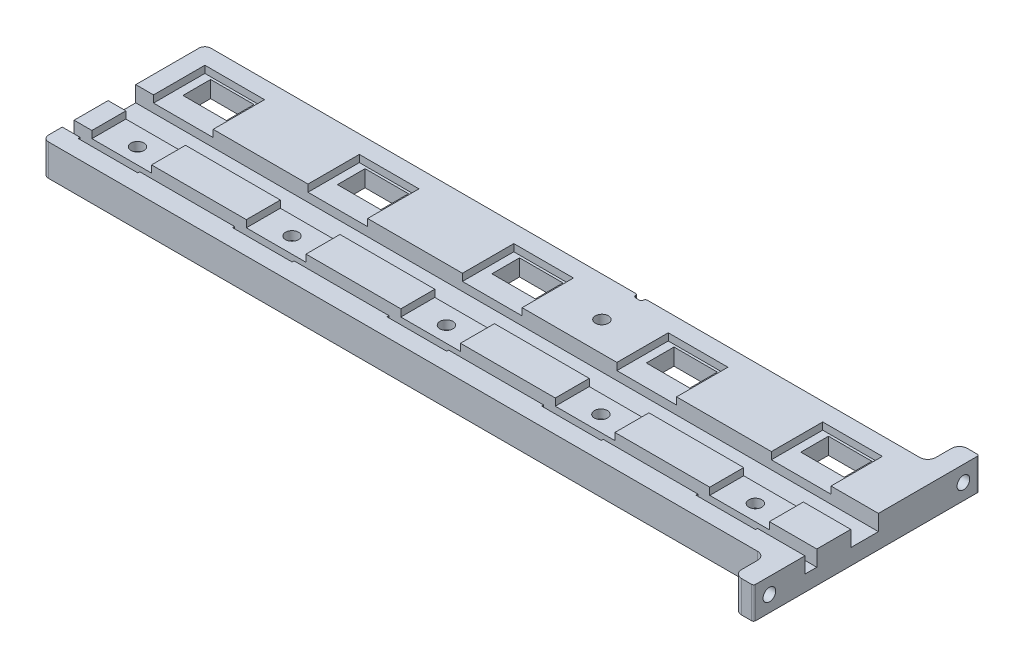
SolidWorks part; units mm, degrees
ref_plane "Front Plane" through (0, 0, 0) normal (0, 0, 1) x (1, 0, 0)
ref_plane "Top Plane" through (0, 0, 0) normal (0, 1, 0) x (1, 0, 0)
ref_plane "Right Plane" through (0, 0, 0) normal (1, 0, 0) x (0, 0, -1)
sketch "Sketch1" plane through (0, 0, 0) normal (0, 1, 0) x (1, 0, 0)
  line L0 (0, 20.55) -> (0, -20.55) construction
  line L1 (-188, 20.55) -> (188, 20.55)
  line L2 (-188, 20.55) -> (-188, -20.55)
  line L3 (-188, -20.55) -> (188, -20.55)
  line L4 (188, 20.55) -> (188, -20.55)
  line L5 (-188, 20.55) -> (188, -20.55) construction
  line L6 (-188, -20.55) -> (188, 20.55) construction
  line L7 (19.55, 20.55) -> (19.55, -20.55) construction
  line L8 (39.3017, 24.4025) -> (39.3017, -16.4975) construction
  line L9 (14.05, 15.45) -> (25.05, 15.45)
  line L10 (14.05, 15.45) -> (14.05, 8.45)
  line L11 (14.05, 8.45) -> (25.05, 8.45)
  line L12 (25.05, 15.45) -> (25.05, 8.45)
  line L13 (14.05, 15.45) -> (25.05, 8.45) construction
  line L14 (14.05, 8.45) -> (25.05, 15.45) construction
  line L15 (12.5, 15.55) -> (26.6, 15.55)
  line L16 (12.5, 15.55) -> (12.5, -15.55)
  line L17 (12.5, -15.55) -> (26.6, -15.55)
  line L18 (26.6, 15.55) -> (26.6, -15.55)
  line L19 (12.5, 15.55) -> (26.6, -15.55) construction
  line L20 (12.5, -15.55) -> (26.6, 15.55) construction
  line L21 (58.65, 20.45) -> (58.65, -20.45) construction
  line L22 (53.15, 15.45) -> (64.15, 15.45)
  line L23 (53.15, 15.45) -> (53.15, 8.45)
  line L24 (53.15, 8.45) -> (64.15, 8.45)
  line L25 (64.15, 15.45) -> (64.15, 8.45)
  line L26 (53.15, 15.45) -> (64.15, 8.45) construction
  line L27 (53.15, 8.45) -> (64.15, 15.45) construction
  line L28 (51.6, 15.55) -> (65.7, 15.55)
  line L29 (51.6, 15.55) -> (51.6, -15.55)
  line L30 (51.6, -15.55) -> (65.7, -15.55)
  line L31 (65.7, 15.55) -> (65.7, -15.55)
  line L32 (51.6, 15.55) -> (65.7, -15.55) construction
  line L33 (51.6, -15.55) -> (65.7, 15.55) construction
  line L34 (2.5, 20.55) -> (2.5, -20.35) construction
  line L35 (-19.55, 20.45) -> (-19.55, -20.45) construction
  line L36 (-25.05, 15.45) -> (-14.05, 15.45)
  line L37 (-25.05, 15.45) -> (-25.05, 8.45)
  line L38 (-25.05, 8.45) -> (-14.05, 8.45)
  line L39 (-14.05, 15.45) -> (-14.05, 8.45)
  line L40 (-25.05, 15.45) -> (-14.05, 8.45) construction
  line L41 (-25.05, 8.45) -> (-14.05, 15.45) construction
  line L42 (-26.6, 15.55) -> (-12.5, 15.55)
  line L43 (-26.6, 15.55) -> (-26.6, -15.55)
  line L44 (-26.6, -15.55) -> (-12.5, -15.55)
  line L45 (-12.5, 15.55) -> (-12.5, -15.55)
  line L46 (-26.6, 15.55) -> (-12.5, -15.55) construction
  line L47 (-26.6, -15.55) -> (-12.5, 15.55) construction
  line L48 (78.3899, 8.6881) -> (78.3899, -32.2119) construction
  line L49 (97.75, 36.3335) -> (97.75, -36.3335) construction
  line L50 (92.25, 15.45) -> (103.25, 15.45)
  line L51 (92.25, 15.45) -> (92.25, 8.45)
  line L52 (92.25, 8.45) -> (103.25, 8.45)
  line L53 (103.25, 15.45) -> (103.25, 8.45)
  line L54 (92.25, 15.45) -> (103.25, 8.45) construction
  line L55 (92.25, 8.45) -> (103.25, 15.45) construction
  line L56 (90.7, 15.55) -> (104.8, 15.55)
  line L57 (90.7, 15.55) -> (90.7, -15.55)
  line L58 (90.7, -15.55) -> (104.8, -15.55)
  line L59 (104.8, 15.55) -> (104.8, -15.55)
  line L60 (90.7, 15.55) -> (104.8, -15.55) construction
  line L61 (90.7, -15.55) -> (104.8, 15.55) construction
  line L62 (-4.3132, 22.4762) -> (-4.3132, -18.4238) construction
  line L63 (-58.65, 23.8204) -> (-58.65, -23.8204) construction
  line L64 (-64.15, 15.45) -> (-53.15, 15.45)
  line L65 (-64.15, 15.45) -> (-64.15, 8.45)
  line L66 (-64.15, 8.45) -> (-53.15, 8.45)
  line L67 (-53.15, 15.45) -> (-53.15, 8.45)
  line L68 (-64.15, 15.45) -> (-53.15, 8.45) construction
  line L69 (-64.15, 8.45) -> (-53.15, 15.45) construction
  line L70 (-65.7, 15.55) -> (-51.6, 15.55)
  line L71 (-65.7, 15.55) -> (-65.7, -15.55)
  line L72 (-65.7, -15.55) -> (-51.6, -15.55)
  line L73 (-51.6, 15.55) -> (-51.6, -15.55)
  line L74 (-65.7, 15.55) -> (-51.6, -15.55) construction
  line L75 (-65.7, -15.55) -> (-51.6, 15.55) construction
  line L76 (-4.3132, 22.4762) -> (-4.3132, -18.4238) construction
  line L77 (-97.75, 23.4723) -> (-97.75, -23.4723) construction
  line L78 (-103.25, 15.45) -> (-92.25, 15.45)
  line L79 (-103.25, 15.45) -> (-103.25, 8.45)
  line L80 (-103.25, 8.45) -> (-92.25, 8.45)
  line L81 (-92.25, 15.45) -> (-92.25, 8.45)
  line L82 (-103.25, 15.45) -> (-92.25, 8.45) construction
  line L83 (-103.25, 8.45) -> (-92.25, 15.45) construction
  line L84 (-104.8, 15.55) -> (-90.7, 15.55)
  line L85 (-104.8, 15.55) -> (-104.8, -15.55)
  line L86 (-104.8, -15.55) -> (-90.7, -15.55)
  line L87 (-90.7, 15.55) -> (-90.7, -15.55)
  line L88 (-104.8, 15.55) -> (-90.7, -15.55) construction
  line L89 (-104.8, -15.55) -> (-90.7, 15.55) construction
  line L90 (-4.3132, 22.4762) -> (-4.3132, -18.4238) construction
  line L91 (-136.85, 23.6913) -> (-136.85, -23.6913) construction
  line L92 (-142.35, 15.45) -> (-131.35, 15.45)
  line L93 (-142.35, 15.45) -> (-142.35, 8.45)
  line L94 (-142.35, 8.45) -> (-131.35, 8.45)
  line L95 (-131.35, 15.45) -> (-131.35, 8.45)
  line L96 (-142.35, 15.45) -> (-131.35, 8.45) construction
  line L97 (-142.35, 8.45) -> (-131.35, 15.45) construction
  line L98 (-143.9, 15.55) -> (-129.8, 15.55)
  line L99 (-143.9, 15.55) -> (-143.9, -15.55)
  line L100 (-143.9, -15.55) -> (-129.8, -15.55)
  line L101 (-129.8, 15.55) -> (-129.8, -15.55)
  line L102 (-143.9, 15.55) -> (-129.8, -15.55) construction
  line L103 (-143.9, -15.55) -> (-129.8, 15.55) construction
  line L104 (-4.3132, 22.4762) -> (-4.3132, -18.4238) construction
  line L105 (-175.95, 23.8593) -> (-175.95, -23.8593) construction
  line L106 (-181.45, 15.45) -> (-170.45, 15.45)
  line L107 (-181.45, 15.45) -> (-181.45, 8.45)
  line L108 (-181.45, 8.45) -> (-170.45, 8.45)
  line L109 (-170.45, 15.45) -> (-170.45, 8.45)
  line L110 (-181.45, 15.45) -> (-170.45, 8.45) construction
  line L111 (-181.45, 8.45) -> (-170.45, 15.45) construction
  line L112 (-183, 15.55) -> (-168.9, 15.55)
  line L113 (-183, 15.55) -> (-183, -15.55)
  line L114 (-183, -15.55) -> (-168.9, -15.55)
  line L115 (-168.9, 15.55) -> (-168.9, -15.55)
  line L116 (-183, 15.55) -> (-168.9, -15.55) construction
  line L117 (-183, -15.55) -> (-168.9, 15.55) construction
  line L118 (-4.3132, 22.4762) -> (-4.3132, -18.4238) construction
  line L119 (136.85, 22.8512) -> (136.85, -22.8512) construction
  line L120 (131.35, 15.45) -> (142.35, 15.45)
  line L121 (131.35, 15.45) -> (131.35, 8.45)
  line L122 (131.35, 8.45) -> (142.35, 8.45)
  line L123 (142.35, 15.45) -> (142.35, 8.45)
  line L124 (131.35, 15.45) -> (142.35, 8.45) construction
  line L125 (131.35, 8.45) -> (142.35, 15.45) construction
  line L126 (129.8, 15.55) -> (143.9, 15.55)
  line L127 (129.8, 15.55) -> (129.8, -15.55)
  line L128 (129.8, -15.55) -> (143.9, -15.55)
  line L129 (143.9, 15.55) -> (143.9, -15.55)
  line L130 (129.8, 15.55) -> (143.9, -15.55) construction
  line L131 (129.8, -15.55) -> (143.9, 15.55) construction
  line L132 (-4.3132, 22.4762) -> (-4.3132, -18.4238) construction
  line L133 (175.95, 22.8773) -> (175.95, -22.8773) construction
  line L134 (170.45, 15.45) -> (181.45, 15.45)
  line L135 (170.45, 15.45) -> (170.45, 8.45)
  line L136 (170.45, 8.45) -> (181.45, 8.45)
  line L137 (181.45, 15.45) -> (181.45, 8.45)
  line L138 (170.45, 15.45) -> (181.45, 8.45) construction
  line L139 (170.45, 8.45) -> (181.45, 15.45) construction
  line L140 (168.9, 15.55) -> (183, 15.55)
  line L141 (168.9, 15.55) -> (168.9, -15.55)
  line L142 (168.9, -15.55) -> (183, -15.55)
  line L143 (183, 15.55) -> (183, -15.55)
  line L144 (168.9, 15.55) -> (183, -15.55) construction
  line L145 (168.9, -15.55) -> (183, 15.55) construction
  circle A0 centre (19.55, -8.55) radius 1.65
  circle A1 centre (58.65, -8.55) radius 1.65
  circle A2 centre (-19.55, -8.55) radius 1.65
  circle A3 centre (97.75, -8.55) radius 1.65
  circle A4 centre (-58.65, -8.55) radius 1.65
  circle A5 centre (-97.75, -8.55) radius 1.65
  circle A6 centre (-136.85, -8.55) radius 1.65
  circle A7 centre (-175.95, -8.55) radius 1.65
  circle A8 centre (136.85, -8.55) radius 1.65
  circle A9 centre (175.95, -8.55) radius 1.65
  point P0 (0, 0)
  point P10 (19.55, 11.95)
  point P17 (19.55, 0)
  point P22 (39.3017, 3.9525)
  point P27 (58.65, 11.95)
  point P34 (58.65, 0)
  point P39 (-8.2824, 0)
  point P44 (-19.55, 11.95)
  point P51 (-19.55, 0)
  point P56 (78.3899, -11.7619)
  point P61 (97.75, 11.95)
  point P68 (97.75, 0)
  point P73 (-4.3132, 2.0262)
  point P78 (-58.65, 11.95)
  point P85 (-58.65, 0)
  point P90 (-4.3132, 2.0262)
  point P95 (-97.75, 11.95)
  point P102 (-97.75, 0)
  point P107 (-4.3132, 2.0262)
  point P112 (-136.85, 11.95)
  point P119 (-136.85, 0)
  point P124 (-4.3132, 2.0262)
  point P129 (-175.95, 11.95)
  point P136 (-175.95, 0)
  point P141 (-4.3132, 2.0262)
  point P146 (136.85, 11.95)
  point P153 (136.85, 0)
  point P158 (-4.3132, 2.0262)
  point P163 (175.95, 11.95)
  point P170 (175.95, 0)
  dimension "D3" = 3.3
  dimension "D7" = 7
  dimension "D11" = 3.3
  dimension "D18" = 3.3
  dimension "D30" = 3.3
  dimension "D37" = 3.3
  dimension "D44" = 3.3
  dimension "D51" = 3.3
  dimension "D58" = 3.3
  dimension "D65" = 3.3
  dimension "D72" = 3.3
  dimension "D95" = 39.1
  dimension "D98" = 7
  dimension "D1" = 7
  dimension "D2" = 11
  dimension "D4" = 31.1
  dimension "D5" = 14.1
  dimension "D6" = 0.1
  dimension "D9" = 7
  dimension "D10" = 11
  dimension "D12" = 31.1
  dimension "D13" = 14.1
  dimension "D14" = 0.1
  dimension "D15" = 7
  dimension "D16" = 7
  dimension "D17" = 11
  dimension "D19" = 31.1
  dimension "D20" = 14.1
  dimension "D21" = 0.1
  dimension "D22" = 7
  dimension "D23" = 25
  dimension "D24" = 25
  dimension "D25" = 5
  dimension "D26" = 5
  dimension "D27" = 25
  dimension "D28" = 7
  dimension "D29" = 11
  dimension "D31" = 31.1
  dimension "D32" = 14.1
  dimension "D33" = 0.1
  dimension "D34" = 7
  dimension "D35" = 7
  dimension "D36" = 11
  dimension "D38" = 31.1
  dimension "D39" = 14.1
  dimension "D40" = 0.1
  dimension "D41" = 7
  dimension "D42" = 7
  dimension "D43" = 11
  dimension "D45" = 31.1
  dimension "D46" = 14.1
  dimension "D47" = 0.1
  dimension "D48" = 7
  dimension "D49" = 7
  dimension "D50" = 11
  dimension "D52" = 31.1
  dimension "D53" = 14.1
  dimension "D54" = 0.1
  dimension "D55" = 7
  dimension "D56" = 7
  dimension "D57" = 11
  dimension "D59" = 31.1
  dimension "D60" = 14.1
  dimension "D61" = 0.1
  dimension "D62" = 7
  dimension "D63" = 7
  dimension "D64" = 11
  dimension "D66" = 31.1
  dimension "D67" = 14.1
  dimension "D68" = 0.1
  dimension "D69" = 7
  dimension "D70" = 7
  dimension "D71" = 11
  dimension "D73" = 31.1
  dimension "D74" = 14.1
  dimension "D75" = 0.1
  dimension "D76" = 7
  dimension "D77" = 25
  dimension "D78" = 25
  dimension "D79" = 25
  dimension "D80" = 5
  dimension "D81" = 25
  dimension "D82" = 5
  dimension "D83" = 25
  dimension "D84" = 25
  dimension "D85" = 5
  dimension "D86" = 5
  dimension "D87" = 5
  dimension "D88" = 5
  dimension "D89" = 5
  dimension "D90" = 10
  dimension "D91" = 5
  dimension "D92" = 5
  dimension "D93" = 5
  dimension "D94" = 5
  dimension "D96" = 1.55
  dimension "D97" = 0.1
extrude "Boss-Extrude1" add sketch "Sketch1" along normal blind 8 contours L4 L1 L2 L3 L126 L129 L128 L127 L98 L101 L100 L99 L70 L73 L72 L71 L42 L45 L44 L43 L15 L18 L17 L16 L28 L31 L30 L29 L56 L59 L58 L57 L84 L87 L86 L85 L112 L115 L114 L113 L140 | L115 L112 L113 L114 A7 L106 L109 L108 L107 | L101 L98 L99 L100 A6 L92 L95 L94 L93 | L87 L84 L85 L86 A5 L78 L81 L80 L79 | L73 L70 L71 L72 A4 L64 L67 L66 L65 | L45 L42 L43 L44 A2 L36 L39 L38 L37 | L31 L28 L29 L30 A1 L22 L25 L24 L23 | L59 L56 L57 L58 A3 L50 L53 L52 L51 | L129 L126 L127 L128 A8 L120 L123 L122 L121 | L143 L140 L141 L142 A9 L134 L137 L136 L135 | L16 L15 L18 L17 | L10 L9 L12 L11 | A0 region at (0, 0, 0) region at (58.65, 0, 2.3998) region at (-19.55, 0, 2.3998) region at (97.75, 0, 2.3998) region at (-58.65, 0, 2.3998) region at (-97.75, 0, 2.3998) region at (-136.85, 0, 2.3998) region at (-175.95, 0, 2.3998) region at (136.85, 0, 2.3998) region at (175.95, 0, 2.3998)
sketch "Sketch2" plane through (0, 8, 0) normal (0, 1, 0) x (1, 0, 0)
  line L0 (-188, 20.55) -> (-188, -20.55) construction
  line L1 (-188, -15.55) -> (188, -15.55)
  line L2 (-188, -15.55) -> (-188, -12.55)
  line L3 (-188, -12.55) -> (188, -12.55)
  line L4 (188, -15.55) -> (188, -12.55)
  line L5 (188, 20.55) -> (188, -20.55) construction
  line L6 (-188, -20.55) -> (188, -20.55) construction
  line L7 (188, -3.95) -> (-188, -3.95)
  line L8 (188, -3.95) -> (188, 3.05)
  line L9 (188, 3.05) -> (-188, 3.05)
  line L10 (-188, -3.95) -> (-188, 3.05)
  dimension "D1" = 5
  dimension "D2" = 3
  dimension "D3" = 8.6
  dimension "D4" = 7
extrude "Cut-Extrude1" cut sketch "Sketch2" against normal blind 4
sketch "Sketch3" plane through (0, 8, 0) normal (0, 1, 0) x (1, 0, 0)
  line L0 (-181.45, 15.45) -> (-170.45, 15.45) construction
  line L1 (-183, 15.55) -> (-168.9, 15.55)
  line L2 (-183, 15.55) -> (-183, -15.55)
  line L3 (-183, -15.55) -> (-168.9, -15.55)
  line L4 (-168.9, 15.55) -> (-168.9, -15.55)
  line L5 (-170.45, 15.45) -> (-170.45, 8.45) construction
  line L6 (-181.45, 15.45) -> (-181.45, 8.45) construction
  line L7 (-188, 20.55) -> (-188, 3.05) construction
  line L9 (-183.5, 16.05) -> (-168.4, 16.05)
  line L10 (-183.5, 16.05) -> (-183.5, -16.05)
  line L11 (-183.5, -16.05) -> (-168.4, -16.05)
  line L12 (-168.4, 16.05) -> (-168.4, -16.05)
  line L84 (-144.4, 16.05) -> (-144.4, -16.05)
  line L85 (-144.4, 16.05) -> (-129.3, 16.05)
  line L86 (-129.3, 16.05) -> (-129.3, -16.05)
  line L87 (-144.4, -16.05) -> (-129.3, -16.05)
  line L88 (-105.3, 16.05) -> (-105.3, -16.05)
  line L89 (-105.3, 16.05) -> (-90.2, 16.05)
  line L90 (-90.2, 16.05) -> (-90.2, -16.05)
  line L91 (-105.3, -16.05) -> (-90.2, -16.05)
  line L92 (-66.2, 16.05) -> (-66.2, -16.05)
  line L93 (-66.2, 16.05) -> (-51.1, 16.05)
  line L94 (-51.1, 16.05) -> (-51.1, -16.05)
  line L95 (-66.2, -16.05) -> (-51.1, -16.05)
  line L96 (-27.1, 16.05) -> (-27.1, -16.05)
  line L97 (-27.1, 16.05) -> (-12, 16.05)
  line L98 (-12, 16.05) -> (-12, -16.05)
  line L99 (-27.1, -16.05) -> (-12, -16.05)
  line L100 (12, 16.05) -> (12, -16.05)
  line L101 (12, 16.05) -> (27.1, 16.05)
  line L102 (27.1, 16.05) -> (27.1, -16.05)
  line L103 (12, -16.05) -> (27.1, -16.05)
  line L104 (51.1, 16.05) -> (51.1, -16.05)
  line L105 (51.1, 16.05) -> (66.2, 16.05)
  line L106 (66.2, 16.05) -> (66.2, -16.05)
  line L107 (51.1, -16.05) -> (66.2, -16.05)
  line L108 (90.2, 16.05) -> (90.2, -16.05)
  line L109 (90.2, 16.05) -> (105.3, 16.05)
  line L110 (105.3, 16.05) -> (105.3, -16.05)
  line L111 (90.2, -16.05) -> (105.3, -16.05)
  line L112 (129.3, 16.05) -> (129.3, -16.05)
  line L113 (129.3, 16.05) -> (144.4, 16.05)
  line L114 (144.4, 16.05) -> (144.4, -16.05)
  line L115 (129.3, -16.05) -> (144.4, -16.05)
  line L116 (168.4, 16.05) -> (168.4, -16.05)
  line L117 (168.4, 16.05) -> (183.5, 16.05)
  line L118 (183.5, 16.05) -> (183.5, -16.05)
  line L119 (168.4, -16.05) -> (183.5, -16.05)
  circle A0 centre (-175.95, -8.55) radius 1.65 construction
  dimension "D4" = 7
  dimension "D1" = 0.1
  dimension "D2" = 1.55
  dimension "D3" = 1.55
  dimension "D5" = 5
  dimension "D6" = 0.5
  dimension "D7" = 0.5
  dimension "D8" = 0.5
  dimension "D9" = 0.5
  dimension "D10" = 10
extrude "Cut-Extrude2" cut sketch "Sketch3" against normal blind 1.8 contours L116 L119 L118 L117 | L112 L115 L114 L113 | L104 L107 L106 L105 | L96 L99 L98 L97 | L88 L91 L90 L89 | L10 L9 L12 L11 | L84 L87 L86 L85 | L92 L95 L94 L93 | L100 L103 L102 L101 | L108 L111 L110 L109
sketch "Sketch5" plane through (0, 8, 0) normal (0, 1, 0) x (1, 0, 0)
  line L0 (0, 20.55) -> (0, -20.55) construction
  line L1 (-188, 20.55) -> (188, 20.55) construction
  line L2 (-188, -20.55) -> (188, -20.55) construction
  line L3 (-77.5, 10.55) -> (77.5, 10.55)
  circle A0 centre (-77.5, 10.55) radius 1.65
  circle A1 centre (77.5, 10.55) radius 1.65
  point P10 (0, 0)
  point P13 (0.1189, 29.0412)
  dimension "D3" = 3.3
  dimension "D4" = 3.3
  dimension "D1" = 155
  dimension "D2" = 10
extrude "Cut-Extrude3" cut sketch "Sketch5" against normal blind 46.5 contours A0 | A1 region at (77.5, 8, -12.1533) region at (-79.1033, 8, -10.55)
chamfer "Chamfer1" distance 2 angle 45 40 edges at (-181.45, 0, -11.95) (-175.95, 0, -8.45) (-170.45, 0, -11.95) (-175.95, 0, -15.45) (-142.35, 0, -11.95) (-136.85, 0, -8.45) (-131.35, 0, -11.95) (-136.85, 0, -15.45) (-103.25, 0, -11.95) (-97.75, 0, -8.45) (-92.25, 0, -11.95) (-97.75, 0, -15.45) (-64.15, 0, -11.95) (-58.65, 0, -8.45) (-53.15, 0, -11.95) (-58.65, 0, -15.45) (-25.05, 0, -11.95) (-19.55, 0, -8.45) (-14.05, 0, -11.95) (-19.55, 0, -15.45) (14.05, 0, -11.95) (19.55, 0, -8.45) (25.05, 0, -11.95) (19.55, 0, -15.45) (53.15, 0, -11.95) (58.65, 0, -8.45) (64.15, 0, -11.95) (58.65, 0, -15.45) (92.25, 0, -11.95) (97.75, 0, -8.45) (103.25, 0, -11.95) (97.75, 0, -15.45) (131.35, 0, -11.95) (136.85, 0, -8.45) (142.35, 0, -11.95) (136.85, 0, -15.45) (175.95, 0, -8.45) (170.45, 0, -11.95) (181.45, 0, -11.95) (175.95, 0, -15.45)
sketch "Sketch6" plane through (0, 0, 0) normal (0, -1, 0) x (1, 0, 0)
  line L0 (-136.85, 5.3168) -> (-134.05, 6.9334)
  line L1 (-175.95, 5.3168) -> (-173.15, 6.9334)
  line L2 (-173.15, 6.9334) -> (-173.15, 10.1666)
  line L3 (-173.15, 10.1666) -> (-175.95, 11.7832)
  line L4 (-175.95, 11.7832) -> (-178.75, 10.1666)
  line L5 (-178.75, 10.1666) -> (-178.75, 6.9334)
  line L6 (-178.75, 6.9334) -> (-175.95, 5.3168)
  line L7 (-134.05, 6.9334) -> (-134.05, 10.1666)
  line L8 (-134.05, 10.1666) -> (-136.85, 11.7832)
  line L9 (-136.85, 11.7832) -> (-139.65, 10.1666)
  line L10 (-139.65, 10.1666) -> (-139.65, 6.9334)
  line L11 (-139.65, 6.9334) -> (-136.85, 5.3168)
  line L12 (-97.75, 5.3168) -> (-94.95, 6.9334)
  line L13 (-94.95, 6.9334) -> (-94.95, 10.1666)
  line L14 (-94.95, 10.1666) -> (-97.75, 11.7832)
  line L15 (-97.75, 11.7832) -> (-100.55, 10.1666)
  line L16 (-100.55, 10.1666) -> (-100.55, 6.9334)
  line L17 (-100.55, 6.9334) -> (-97.75, 5.3168)
  line L18 (-58.65, 5.3168) -> (-55.85, 6.9334)
  line L19 (-55.85, 6.9334) -> (-55.85, 10.1666)
  line L20 (-55.85, 10.1666) -> (-58.65, 11.7832)
  line L21 (-58.65, 11.7832) -> (-61.45, 10.1666)
  line L22 (-61.45, 10.1666) -> (-61.45, 6.9334)
  line L23 (-61.45, 6.9334) -> (-58.65, 5.3168)
  line L24 (-19.55, 5.3168) -> (-16.75, 6.9334)
  line L25 (-16.75, 6.9334) -> (-16.75, 10.1666)
  line L26 (-16.75, 10.1666) -> (-19.55, 11.7832)
  line L27 (-19.55, 11.7832) -> (-22.35, 10.1666)
  line L28 (-22.35, 10.1666) -> (-22.35, 6.9334)
  line L29 (-22.35, 6.9334) -> (-19.55, 5.3168)
  line L30 (19.55, 5.3168) -> (22.35, 6.9334)
  line L31 (22.35, 6.9334) -> (22.35, 10.1666)
  line L32 (22.35, 10.1666) -> (19.55, 11.7832)
  line L33 (19.55, 11.7832) -> (16.75, 10.1666)
  line L34 (16.75, 10.1666) -> (16.75, 6.9334)
  line L35 (16.75, 6.9334) -> (19.55, 5.3168)
  line L36 (58.65, 5.3168) -> (61.45, 6.9334)
  line L37 (61.45, 6.9334) -> (61.45, 10.1666)
  line L38 (61.45, 10.1666) -> (58.65, 11.7832)
  line L39 (58.65, 11.7832) -> (55.85, 10.1666)
  line L40 (55.85, 10.1666) -> (55.85, 6.9334)
  line L41 (55.85, 6.9334) -> (58.65, 5.3168)
  line L42 (97.75, 5.3168) -> (100.55, 6.9334)
  line L43 (100.55, 6.9334) -> (100.55, 10.1666)
  line L44 (100.55, 10.1666) -> (97.75, 11.7832)
  line L45 (97.75, 11.7832) -> (94.95, 10.1666)
  line L46 (94.95, 10.1666) -> (94.95, 6.9334)
  line L47 (94.95, 6.9334) -> (97.75, 5.3168)
  line L48 (136.85, 5.3168) -> (139.65, 6.9334)
  line L49 (139.65, 6.9334) -> (139.65, 10.1666)
  line L50 (139.65, 10.1666) -> (136.85, 11.7832)
  line L51 (136.85, 11.7832) -> (134.05, 10.1666)
  line L52 (134.05, 10.1666) -> (134.05, 6.9334)
  line L53 (134.05, 6.9334) -> (136.85, 5.3168)
  line L54 (175.95, 5.3168) -> (178.75, 6.9334)
  line L55 (178.75, 6.9334) -> (178.75, 10.1666)
  line L56 (178.75, 10.1666) -> (175.95, 11.7832)
  line L57 (175.95, 11.7832) -> (173.15, 10.1666)
  line L58 (173.15, 10.1666) -> (173.15, 6.9334)
  line L59 (173.15, 6.9334) -> (175.95, 5.3168)
  circle A0 centre (-175.95, 8.55) radius 2.8 construction
  dimension "D1" = 5.6
  dimension "D2" = 10
extrude "Cut-Extrude4" cut sketch "Sketch6" against normal blind 4
fillet "Fillet1" radius 1.5 4 edges at (-188, 4, -20.55) (188, 4, -20.55) (188, 4, 20.55) (-188, 4, 20.55)
sketch "Sketch7" plane through (0, 8, 0) normal (0, 1, 0) x (1, 0, 0)
  line L0 (0, 20.55) -> (0, -20.55) construction
  line L1 (-186.5, 20.55) -> (186.5, 20.55) construction
  line L2 (-186.5, -20.55) -> (186.5, -20.55) construction
  line L4 (0, 20.55) -> (188, 20.55)
  line L5 (0, 20.55) -> (0, -20.55)
  line L6 (0, -20.55) -> (188, -20.55)
  line L7 (188, 20.55) -> (188, -20.55)
extrude "Cut-Extrude5" cut sketch "Sketch7" against normal blind 70
sketch "Sketch8" plane through (0, 8, 0) normal (0, 1, 0) x (1, 0, 0)
  line L1 (0, 20.55) -> (-5, 20.55)
  line L2 (0, 20.55) -> (0, 28.55)
  line L3 (0, 28.55) -> (-5, 28.55)
  line L4 (-5, 20.55) -> (-5, 28.55)
  line L5 (0, -20.55) -> (-5, -20.55)
  line L6 (0, -20.55) -> (0, -28.55)
  line L7 (0, -28.55) -> (-5, -28.55)
  line L8 (-5, -20.55) -> (-5, -28.55)
  dimension "D1" = 5
  dimension "D2" = 5
  dimension "D3" = 8
  dimension "D4" = 8
extrude "Boss-Extrude2" add sketch "Sketch8" against normal blind 8
sketch "Sketch9" plane through (-5, 0, 0) normal (-1, 0, 0) x (0, 0, 1)
  line L0 (24.55, 8) -> (24.55, 0) construction
  line L1 (20.55, 8) -> (28.55, 8) construction
  line L2 (20.55, 0) -> (28.55, 0) construction
  line L3 (-24.55, 8) -> (-24.55, 0) construction
  line L4 (-28.55, 8) -> (-20.55, 8) construction
  line L5 (-28.55, 0) -> (-20.55, 0) construction
  circle A0 centre (-24.55, 4) radius 1.6
  circle A1 centre (24.55, 4) radius 1.6
  dimension "D1" = 3.2
  dimension "D2" = 3.2
extrude "Cut-Extrude6" cut sketch "Sketch9" against normal blind 8
fillet "Fillet2" radius 0.5 2 edges at (0, 4, -28.55) (0, 4, 28.55)
fillet "Fillet3" radius 2 4 edges at (-5, 4, -28.55) (-5, 4, -20.55) (-5, 4, 28.55) (-5, 4, 20.55)
sketch "Sketch11" plane through (0, 8, 0) normal (0, 1, 0) x (1, 0, 0)
  line L0 (-77.5, 12.2) -> (-77.5, 20.55) construction
  line L1 (-186.5, 20.55) -> (-7, 20.55) construction
  line L3 (-78.5, 21.55) -> (-76.5, 21.55)
  line L4 (-78.5, 21.55) -> (-78.5, 19.55)
  line L5 (-78.5, 19.55) -> (-76.5, 19.55)
  line L6 (-76.5, 21.55) -> (-76.5, 19.55)
  line L7 (-78.5, 21.55) -> (-76.5, 19.55) construction
  line L8 (-78.5, 19.55) -> (-76.5, 21.55) construction
  circle A0 centre (-77.5, 10.55) radius 1.65 construction
  dimension "D1" = 2
  dimension "D2" = 2
extrude "Cut-Extrude7" cut sketch "Sketch11" against normal blind 13
fillet "Fillet4" radius 0.5 4 edges at (-78.5, 4, -20.55) (-78.5, 4, -19.55) (-76.5, 4, -19.55) (-76.5, 4, -20.55)
